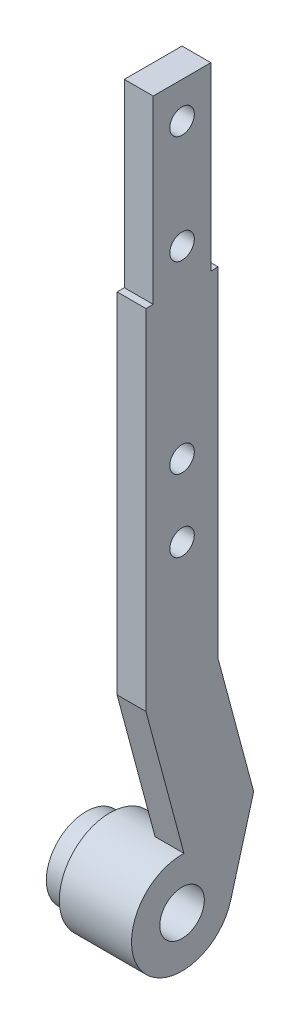
SolidWorks part; units mm, degrees
ref_plane "Front" through (0, 0, 0) normal (0, 0, 1) x (1, 0, 0)
ref_plane "Top" through (0, 0, 0) normal (0, 1, 0) x (1, 0, 0)
ref_plane "Right" through (0, 0, 0) normal (1, 0, 0) x (0, 0, -1)
sketch "Sketch1" plane through (-20.145, 0, 0) normal (-1, 0, 0) x (0, 0, 1)
  line L0 (-5, 27.967) -> (-9.926, 9.5831)
  line L1 (5, 26.6505) -> (5, 100)
  line L2 (5, 100) -> (-5, 100)
  line L3 (-5, 100) -> (-5, 27.967)
  line L4 (-0.2667, 6.9949) -> (5, 26.6505)
  line L5 (-9.926, 9.5831) -> (-6.7448, -1.8729)
  line L6 (5, 75) -> (-5, 75) construction
  line L7 (0, 0) -> (0, 100) construction
  line L8 (-5, 87.5) -> (5, 87.5) construction
  line L9 (0, 95) -> (0, 80) construction
  line L10 (-5, 75) -> (-4, 75)
  line L11 (-4, 75) -> (-4, 100)
  line L12 (5, 75) -> (4, 75)
  line L13 (4, 75) -> (4, 100)
  circle A0 centre (0, 80) radius 1.7
  circle A1 centre (0, 95) radius 1.7
  circle A6 centre (0, 0) radius 3.0845
  arc A7 (-3.0391, 0.5274) -> (2.6861, -1.5163) centre (0, 0) ccw
  arc A8 (-3.0391, 0.5274) -> (2.6861, -1.5163) centre (0, 0) ccw construction
  circle A9 centre (0, 0) radius 7
  point P20 (0, 87.5)
  dimension "D2" = 14
  dimension "D7" = 3.4
  dimension "D8" = 3.4
  dimension "D3" = 10
  dimension "D4" = 10
  dimension "D5" = 10
  dimension "D6" = 100
  dimension "D9" = 15
  dimension "D10" = 25
  dimension "D11" = 1
  dimension "D1" = 0.1
extrude "Boss-Extrude1" add sketch "Sketch1" along normal blind 10 contours A9 A6 region at (-20.145, 4.0124, -5.4925)
extrude "Boss-Extrude2" add sketch "Sketch1<3>" against normal blind 3 from surface contours A9 starting at face at (-30.145, 0, 3.0845)
sketch "Sketch1<3>" plane through (-20.145, 0, 0) normal (-1, 0, 0) x (0, 0, 1) same geometry as "Sketch1"
extrude "Boss-Extrude3" add sketch "Sketch1<5>" along normal blind 4 contours A9 L4 L1 L2 L3 L0 L5 region at (-20.145, 49.6264, -0.767)
sketch "Sketch1<5>" plane through (-20.145, 0, 0) normal (-1, 0, 0) x (0, 0, 1) same geometry as "Sketch1"
sketch "Sketch2" plane through (-30.145, 0, 0) normal (-1, 0, 0) x (0, 0, 1)
  circle A1 centre (0, 0) radius 5.5
  circle A2 centre (0, 0) radius 3.5
  circle A3 centre (0, 0) radius 3.5
  dimension "D1" = 2
  dimension "D2" = 2
extrude "Boss-Extrude4" add sketch "Sketch2" along normal up to surface (3.305 mm away)
sketch "Sketch3" plane through (-20.145, 0, 0) normal (1, 0, 0) x (0, 0, -1)
  circle A0 centre (0, 44.4879) radius 1.7
  circle A1 centre (0, 54.4879) radius 1.7
  circle A3 centre (0, 54.4879) radius 1.7 construction
  circle A4 centre (0, 44.4879) radius 1.7 construction
  point P1 (-1.8505, 56.3706)
  point P4 (-0.8227, 46.9124)
  point P10 (0, 0)
  dimension "D3" = 3.4
  dimension "D4" = 3.4
extrude "Cut-Extrude1" cut sketch "Sketch3" against normal up to surface (4 mm away) contours A1 | A0 up to face at (-24.145, 51.8992, -1.7349)
equation "\"D4@Sketch3\"=\"D3@Sketch3\""
